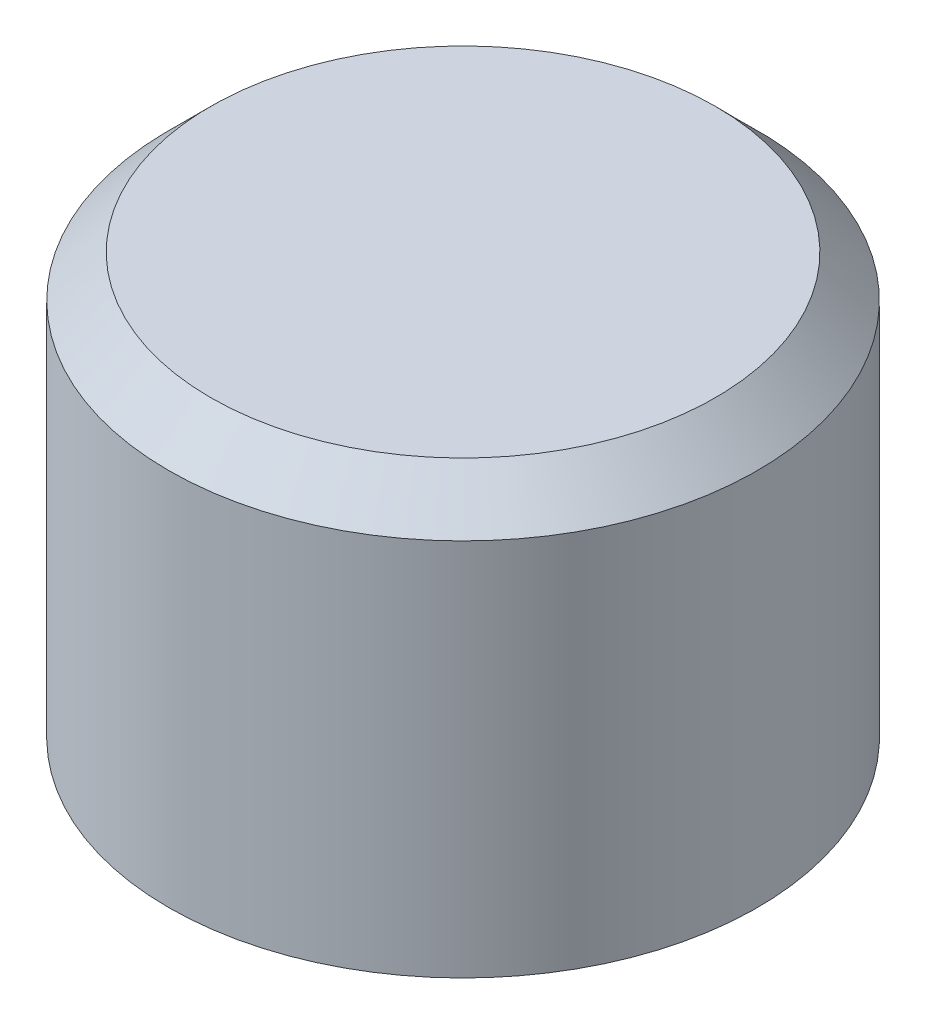
SolidWorks part; units mm, degrees
ref_plane "前视基准面" through (0, 0, 0) normal (0, 0, 1) x (1, 0, 0)
ref_plane "上视基准面" through (0, 0, 0) normal (0, 1, 0) x (1, 0, 0)
ref_plane "右视基准面" through (0, 0, 0) normal (1, 0, 0) x (0, 0, -1)
sketch "草图1" plane through (0, 0, 0) normal (0, 1, 0) x (1, 0, 0)
  circle A0 centre (0, 0) radius 7
extrude "凸台-拉伸1" add sketch "草图1" along normal blind 10 contours A0
sketch "草图2" plane through (0, 0, 0) normal (0, -1, 0) x (1, 0, 0)
  line L0 (0, -1.25) -> (1.1112, -1.25) construction
  line L1 (0, 1.25) -> (1.6756, 1.25) construction
  line L2 (-0.8292, 1.25) -> (0.8292, 1.25)
  line L3 (-0.8292, -1.25) -> (0.8292, -1.25)
  arc A0 (-0.8292, 1.25) -> (-0.8292, -1.25) centre (0, 0) ccw
  circle A1 centre (0, 0) radius 1.25 construction
  arc A2 (0.8292, -1.25) -> (0.8292, 1.25) centre (0, 0) ccw
  point P7 (-0.8292, 1.25)
extrude "切除-拉伸1" cut sketch "草图2" against normal blind 1.5
chamfer "倒角1" distance 1 angle 45 1 edges at (0, 10, 7)
